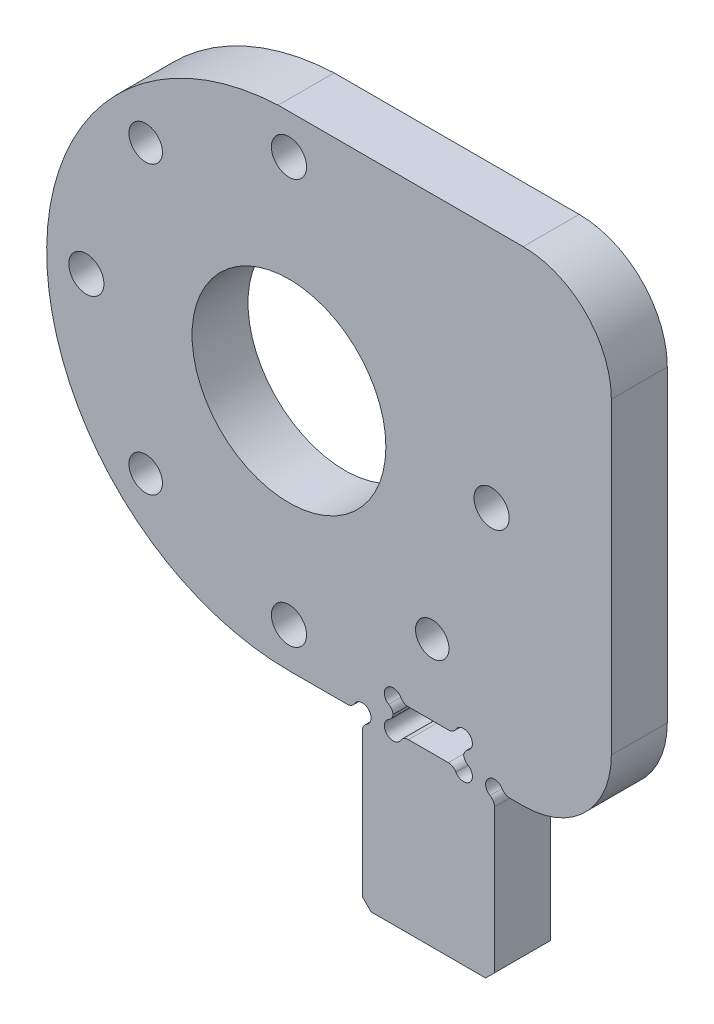
SolidWorks part; units mm, degrees
material "Balsa"
ref_plane "Front Plane" through (0, 0, 0) normal (0, 0, 1) x (1, 0, 0)
ref_plane "Top Plane" through (0, 0, 0) normal (0, 1, 0) x (1, 0, 0)
ref_plane "Right Plane" through (0, 0, 0) normal (1, 0, 0) x (0, 0, -1)
sketch "Sketch1" plane through (0, 0, 0) normal (0, 0, 1) x (1, 0, 0)
  line L0 (-18.0546, 94.4454) -> (-37.5, 75) construction
  line L1 (-40.4988, 0) -> (0, 0)
  line L2 (-75, 55) -> (-75, 75)
  line L3 (-40.4988, 0) -> (-83.323, 0)
  line L4 (0, 0) -> (0, 75)
  line L5 (-37.5, 75) -> (-10, 75) construction
  line L6 (-75, 75) -> (0, 0) construction
  line L7 (-56.9454, 94.4454) -> (-37.5, 75) construction
  line L8 (-75, 55) -> (-83.323, 55)
  line L9 (-37.5, 75) -> (-56.9454, 55.5546) construction
  line L10 (-83.323, 27.5) -> (-83.323, 50.5) construction
  arc A0 (-75, 75) -> (0, 75) centre (-37.5, 75) cw
  arc A1 (-83.323, 55) -> (-83.323, 0) centre (-83.323, 27.5) ccw
  circle A2 centre (-83.323, 27.5) radius 11
  circle A3 centre (-37.5, 75) radius 16.5 construction
  circle A4 centre (-83.323, 27.5) radius 23 construction
  circle A5 centre (-67.0596, 11.2365) radius 1.8987
  circle A6 centre (-83.323, 50.5) radius 1.9939
  circle A7 centre (-99.5865, 11.2365) radius 1.8987
  circle A8 centre (-60.323, 27.5) radius 1.9939
  circle A9 centre (-99.5865, 43.7635) radius 1.8987
  circle A10 centre (-83.323, 4.5) radius 1.9939
  circle A11 centre (-106.323, 27.5) radius 1.9939
  circle A13 centre (-37.5, 75) radius 27.5 construction
  circle A14 centre (-37.5, 102.5) radius 1.75 construction
  circle A15 centre (-10, 75) radius 1.75 construction
  circle A16 centre (-37.5, 47.5) radius 1.75 construction
  circle A17 centre (-65, 75) radius 1.75 construction
  circle A18 centre (-18.0546, 94.4454) radius 1.5 construction
  circle A19 centre (-18.0546, 55.5546) radius 1.5 construction
  circle A20 centre (-56.9454, 55.5546) radius 1.5 construction
  circle A21 centre (-56.9454, 94.4454) radius 1.5 construction
  circle A23 centre (-67.0596, 43.7635) radius 1.8987 [skipped]
  point P0 (0, 0)
  point P42 (-83.323, 27.5)
  dimension "D3" = 27.5
  dimension "D5" = 33
  dimension "D6" = 22
  dimension "D7" = 46
  dimension "D9" = 3.7973
  dimension "D10" = 4
  dimension "D12" = 55
  dimension "D14" = 3
  dimension "D16" = 3.5
  dimension "D8" = 3.9878
  dimension "D1" = 75
  dimension "D2" = 66
  dimension "D4" = 75
  dimension "D13" = 45
  dimension "D11" = 4
  dimension "D15" = 4
extrude "Boss-Extrude1" add sketch "Sketch1" along normal blind 6.35
fillet "Fillet1" radius 10 1 edges at (-75, 55, 3.175)
sketch "Sketch2" plane through (0, 0, 0) normal (0, 0, -1) x (-1, 0, 0)
  line L0 (83.323, 0) -> (0, 0) construction
  line L1 (0, 0) -> (15, 0)
  line L2 (0, 0) -> (0, -19.05)
  line L3 (0, -19.05) -> (15, -19.05)
  line L4 (15, 0) -> (15, -19.05)
  line L5 (30, 0) -> (45, 0)
  line L6 (30, 0) -> (30, -19.05)
  line L7 (30, -19.05) -> (45, -19.05)
  line L8 (45, 0) -> (45, -19.05)
  line L10 (60, 0) -> (75, 0)
  line L11 (60, 0) -> (60, -19.05)
  line L12 (60, -19.05) -> (75, -19.05)
  line L13 (75, 0) -> (75, -19.05)
  dimension "D1" = 15
  dimension "D2" = 15
  dimension "D3" = 19.05
  dimension "D4" = 15
extrude "Boss-Extrude2" add sketch "Sketch2" against normal up to surface (6.35 mm away) up to face at (-57.125, 50.8196, 6.35)
chamfer "Chamfer1" distance 1 angle 45 6 edges at (0, -19.05, 3.175) (-15, -19.05, 3.175) (-30, -19.05, 3.175) (-45, -19.05, 3.175) (-60, -19.05, 3.175) (-75, -19.05, 3.175)
sketch "Sketch3" plane through (0, 0, 6.35) normal (0, 0, 1) x (1, 0, 0)
  circle A0 centre (-75, 0) radius 1
  circle A1 centre (-60, 0) radius 1
  circle A2 centre (-45, 0) radius 1
  circle A3 centre (-30, 0) radius 1
  circle A4 centre (-15, 0) radius 1
  dimension "D1" = 2
extrude "Cut-Extrude1" cut sketch "Sketch3" against normal through all
other "Move Face1" [suppressed] offset 0.08 parameters "D1"=0.08
fillet "Fillet2" [suppressed] radius 1
sketch "Sketch4" plane through (0, 0, 6.35) normal (0, 0, 1) x (1, 0, 0)
  line L0 (-67.5, -19.05) -> (-67.5, 8.0214) construction
  line L1 (-71.4967, 0) -> (-63.5033, 0)
  line L2 (-71.4967, 0) -> (-71.4967, 3.2207)
  line L3 (-71.4967, 3.2207) -> (-63.5033, 3.2207)
  line L4 (-63.5033, 0) -> (-63.5033, 3.2207)
  line L5 (-74, -19.05) -> (-61, -19.05) construction
  point P10 (-67.5, 0)
  dimension "D1" = 7.9934
  dimension "D3" = 3.2207
extrude "Cut-Extrude2" cut sketch "Sketch4" against normal through all
fillet "Fillet3" radius 1 10 edges at (-15, -1, 3.175) (-16, 0, 3.175) (-29, 0, 3.175) (-30, -1, 3.175) (-45, -1, 3.175) (-46, 0, 3.175) (-59, 0, 3.175) (-60, -1, 3.175) (-75, -1, 3.175) (-76, 0, 3.175)
sketch "Sketch5" plane through (0, 0, 0) normal (0, 0, -1) x (-1, 0, 0)
  line L0 (46.7321, 0) -> (46.7321, 54.9725)
  line L1 (46.7321, 54.9725) -> (84.5528, 54.9725)
  line L2 (46.7321, 0) -> (46.7321, -19.05)
  line L3 (84.5528, 54.9725) -> (84.5528, 112.5)
  line L4 (84.5528, 112.5) -> (0, 112.5)
  line L5 (0, 112.5) -> (0, -19.05)
  line L6 (0, -19.05) -> (46.7321, -19.05)
  line L7 (31, -19.05) -> (44, -19.05) construction
  line L8 (0, -18.05) -> (0, 75) construction
  arc A0 (75, 75) -> (0, 75) centre (37.5, 75) ccw construction
extrude "Cut-Extrude3" cut sketch "Sketch5" against normal through all
fillet "Fillet4" radius 10 2 edges at (-46.7321, 54.9725, 3.175) (-46.7321, 0, 3.175)
sketch "Sketch9" plane through (0, 0, 6.35) normal (0, 0, 1) x (1, 0, 0)
  circle A0 centre (-71.4967, 3.2207) radius 1
  circle A1 centre (-63.5033, 3.2207) radius 1
  circle A2 centre (-63.5033, 0) radius 1
  circle A3 centre (-71.4967, 0) radius 1
  dimension "D1" = 2
extrude "Cut-Extrude4" cut sketch "Sketch9" against normal through all
fillet "Fillet5" radius 1 8 edges at (-64.5033, 3.2207, 3.175) (-63.5033, 2.2207, 3.175) (-63.5033, 1, 3.175) (-64.5033, 0, 3.175) (-70.4967, 0, 3.175) (-71.4967, 1, 3.175) (-71.4967, 2.2207, 3.175) (-70.4967, 3.2207, 3.175)
